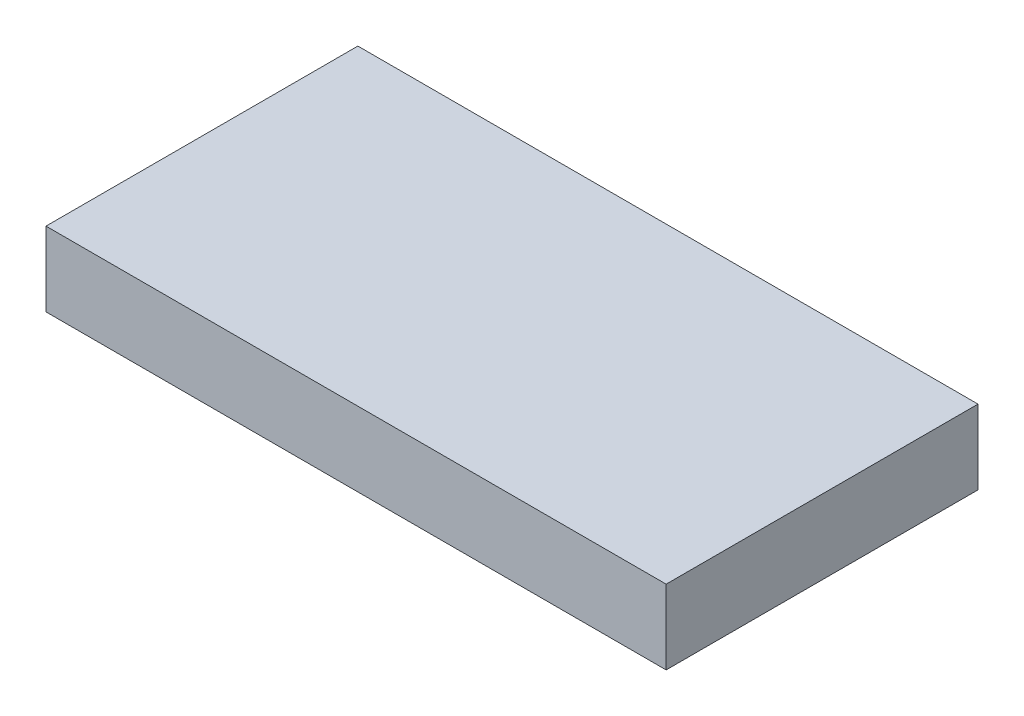
SolidWorks part; units mm, degrees
material "AISI 1020"
ref_plane "Plano frontal" through (0, 0, 0) normal (0, 0, 1) x (1, 0, 0)
ref_plane "Plano superior" through (0, 0, 0) normal (0, 1, 0) x (1, 0, 0)
ref_plane "Plano direito" through (0, 0, 0) normal (1, 0, 0) x (0, 0, -1)
sketch "Esboço1" plane through (0, 0, 0) normal (0, 1, 0) x (1, 0, 0)
  line L1 (-39.77, -20) -> (39.77, -20)
  line L2 (-39.77, -20) -> (-39.77, 20)
  line L3 (-39.77, 20) -> (39.77, 20)
  line L4 (39.77, -20) -> (39.77, 20)
  line L5 (-39.77, -20) -> (39.77, 20) construction
  line L6 (-39.77, 20) -> (39.77, -20) construction
  point P0 (0, 0)
  dimension "D1" = 40
  dimension "D2" = 79.54
base flange "Flange-base1" sketch "Esboço1" thickness 9.53 reverse thickness direction no parameters "D1"=0.7366
sketch "Curva-Linhas1" [suppressed] plane through (0, 0, 0) normal (0, 1, 0) x (1, 0, 0)
sketch "Caixa delimitadora1" [suppressed] plane through (0, 0, 0) normal (0, 1, 0) x (1, 0, 0)
sheet metal parameters "Chapa metálica1" thickness 9.53 parameters "D1"=0.7366
flat pattern "Padrão-Plano1" [suppressed]
sketch "Curva-Linhas2" plane through (0, 0, 0) normal (0, 1, 0) x (1, 0, 0)
sketch3d "Caixa delimitadora2" [suppressed]
  line L0 (-39.77, 20, 0) -> (39.77, 20, 0) construction
  line L1 (-39.77, -20, 0) -> (39.77, -20, 0) construction
  line L2 (-39.77, 20, 0) -> (-39.77, -20, 0) construction
  line L3 (39.77, 20, 0) -> (39.77, -20, 0) construction
